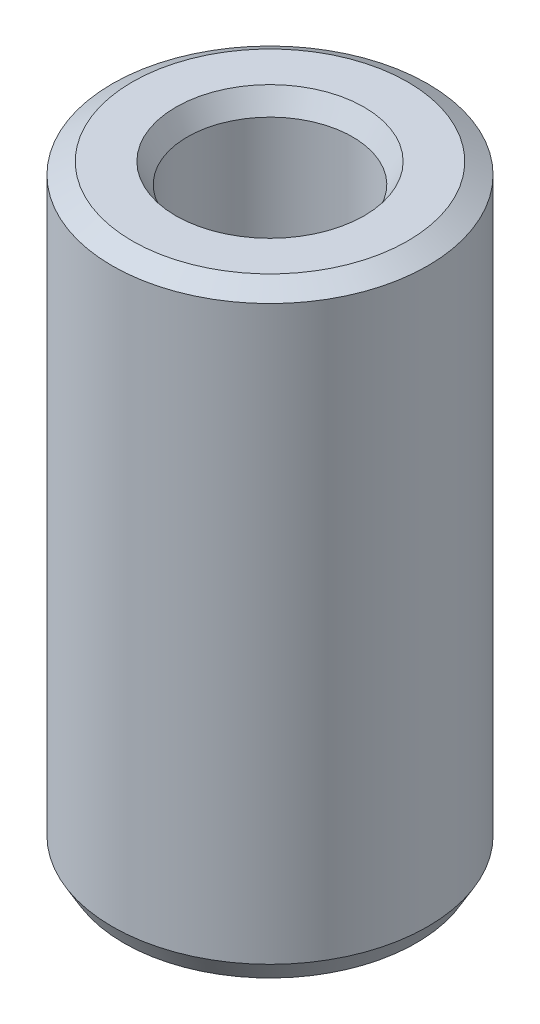
SolidWorks part; units mm, degrees
ref_plane "Front Plane" through (0, 0, 0) normal (0, 0, 1) x (1, 0, 0)
ref_plane "Top Plane" through (0, 0, 0) normal (0, 1, 0) x (1, 0, 0)
ref_plane "Right Plane" through (0, 0, 0) normal (1, 0, 0) x (0, 0, -1)
sketch "Sketch1" plane through (0, 0, 0) normal (0, 1, 0) x (1, 0, 0)
  circle A0 centre (0, 0) radius 37.5
  dimension "SLEEVE_OD" = 75
extrude "Boss-Extrude1" add sketch "Sketch1" along normal blind 143.5465
sketch "Sketch2" plane through (0, 0, 0) normal (0, 1, 0) x (1, 0, 0)
  circle A0 centre (0, 0) radius 19.6381
  dimension "BORE_D" = 39.2763
extrude "Cut-Extrude1" cut sketch "Sketch2" along normal through all
chamfer "Chamfer1" distance 2.7448 angle 60 4 edges at (0, 143.5465, 19.6381) (0, 0, 19.6381) (0, 0, 37.5) (0, 143.5465, 37.5) first distance on face at (0, 143.5465, 19.6381) first distance on face at (0, 0, 19.6381) first distance on face at (0, 143.5465, 37.5)
